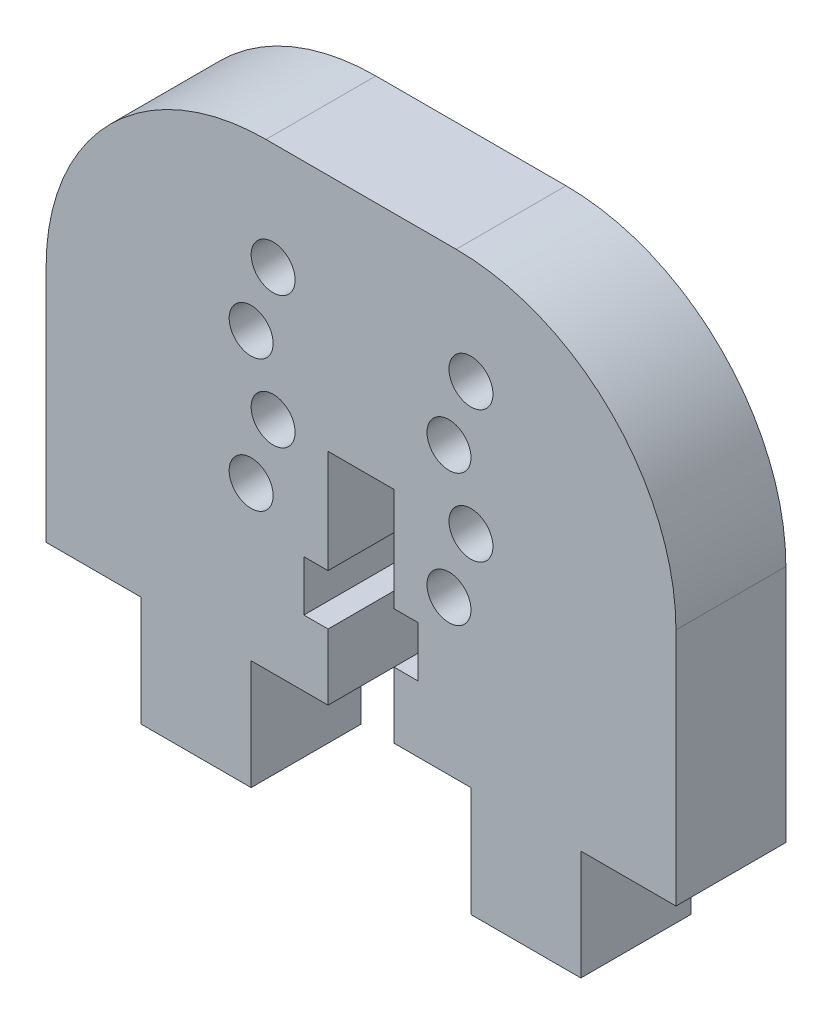
SolidWorks part; units mm, degrees
ref_plane "Front Plane" through (0, 0, 0) normal (0, 0, 1) x (1, 0, 0)
ref_plane "Top Plane" through (0, 0, 0) normal (0, 1, 0) x (1, 0, 0)
ref_plane "Right Plane" through (0, 0, 0) normal (1, 0, 0) x (0, 0, -1)
sketch "Sketch1" plane through (0, 0, 0) normal (0, 0, 1) x (1, 0, 0)
  line L0 (0, 0) -> (0, -10.438) construction
  line L1 (-14.3267, -10.438) -> (14.3267, -10.438)
  line L2 (-14.3267, -10.438) -> (-14.3267, 10.438)
  line L3 (-14.3267, 10.438) -> (14.3267, 10.438)
  line L4 (14.3267, -10.438) -> (14.3267, 10.438)
  line L5 (-14.3267, -10.438) -> (14.3267, 10.438) construction
  line L6 (-14.3267, 10.438) -> (14.3267, -10.438) construction
  line L7 (-4, -0.438) -> (-4, -9.4486) construction
  line L8 (-5, -3.438) -> (-5, -9.4486) construction
  line L9 (4, -3.438) -> (4, 2.562) construction
  line L10 (5, -0.438) -> (5, 5.562) construction
  line L11 (-5, -3.438) -> (4, -3.438) construction
  circle A0 centre (-5, -3.438) radius 1
  circle A1 centre (-4, -0.438) radius 1
  circle A2 centre (-5, 2.562) radius 1
  circle A3 centre (-4, 5.562) radius 1
  circle A4 centre (4, -3.438) radius 1
  circle A5 centre (5, -0.438) radius 1
  circle A6 centre (4, 2.562) radius 1
  circle A7 centre (5, 5.562) radius 1
  point P0 (0, 0)
  line B0 (-2.6, -7.438) -> (-2.6, -5.138)
  line B1 (1.5, -5.138) -> (1.5, -0.438)
  line B2 (-1.5, -0.438) -> (-1.5, -5.138)
  line B3 (-2.6, -5.138) -> (-1.5, -5.138)
  line B4 (0, -10.438) -> (0, 0.7828) construction
  line B5 (-1.5, -10.438) -> (-5, -10.438)
  line B6 (-5, -15.438) -> (-10, -15.438)
  line B7 (-10, -15.438) -> (-10, -10.438)
  line B8 (-5, -15.438) -> (-5, -10.438)
  line B9 (1.5, -10.438) -> (5, -10.438)
  line B10 (5, -10.438) -> (5, -15.438)
  line B11 (5, -15.438) -> (10, -15.438)
  line B12 (10, -15.438) -> (10, -10.438)
  line B13 (-1.5, -10.438) -> (1.5, -10.438) construction
  line B14 (1.5, -10.438) -> (1.5, -7.438)
  line B15 (1.5, -5.138) -> (2.6, -5.138)
  line B16 (2.6, -7.438) -> (1.5, -7.438)
  line B17 (1.5, -0.438) -> (-1.5, -0.438)
  line B18 (-1.5, -7.438) -> (-2.6, -7.438)
  line B19 (2.6, -5.138) -> (2.6, -7.438)
  line B20 (-1.5, -7.438) -> (-1.5, -10.438)
  line B21 (0, -0.438) -> (0, -10.438) construction
  dimension "D1" = 5
  dimension "D5" = 2
  dimension "D2" = 7
  dimension "D3" = 3
  dimension "D4" = 4
  dimension "D6" = 3
  dimension "D7" = 3
  dimension "D8" = 9
  dimension "D9" = 9
sketch_block_instance "Insert M3 plots ep 5mm-1"
sketch_block "Insert M3 plots ep 5mm" parameters "D1"=10, "D2"=5, "D3"=5
sketch_block_instance "Decoupe Insert M3-4"
sketch_block "Block1" parameters "D1"=5.2, "D2"=3, "D3"=2.3, "D4"=3, "D5"=10
extrude "Boss-Extrude1" add sketch "Sketch1" along normal blind 5 contours B20 B18 B0 B3 B2 B17 B1 B15 B19 B16 B14 L1 L4 L3 L2 A7 A6 A5 A4 A3 A2 A1 A0 | B6 B8 L1 B7 | B11 B12 L1 B10 region at (0, 0.3128, 0) region at (-7.5, -12.938, 0) region at (7.5, -12.938, 0)
fillet "Fillet1" radius 10 2 edges at (14.3267, 10.438, 2.5) (-14.3267, 10.438, 2.5)
